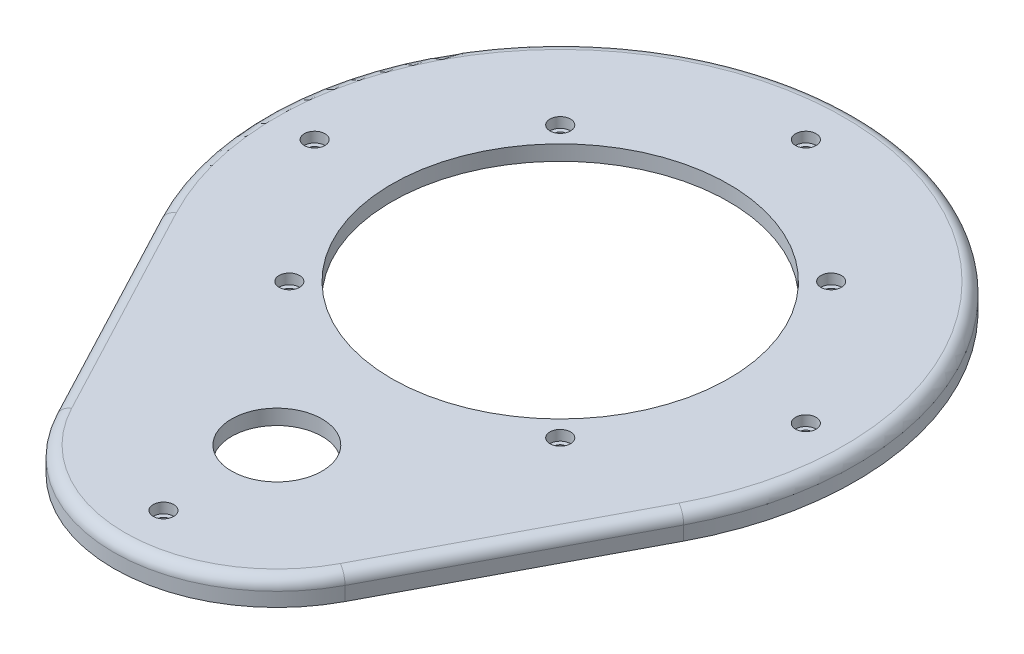
SolidWorks part; units mm, degrees
note: The reader was unsure of these and kept them because the rebuilt part matched: shared geometry of "Sketch1<3>", "Sketch1<4>", "Sketch1<5>".
ref_plane "Front Plane" through (0, 0, 0) normal (0, 0, 1) x (1, 0, 0)
ref_plane "Top Plane" through (0, 0, 0) normal (0, 1, 0) x (1, 0, 0)
ref_plane "Right Plane" through (0, 0, 0) normal (1, 0, 0) x (0, 0, -1)
sketch "Sketch1" plane through (0, 0, 0) normal (0, 1, 0) x (1, 0, 0)
  line L0 (-66.3325, -35) -> (-35.3773, -93.6667)
  line L1 (35.3773, -93.6667) -> (66.3325, -35)
  line L2 (38.2075, -95.16) -> (69.1627, -36.4933)
  line L3 (-69.1627, -36.4933) -> (-38.2075, -95.16)
  line L4 (35.5542, -93.76) -> (66.5094, -35.0933)
  line L5 (-66.5094, -35.0933) -> (-35.5542, -93.76)
  circle A0 centre (0, 0) radius 44.595
  circle A1 centre (-35.85, 35.85) radius 1.6
  circle A2 centre (35.85, 35.85) radius 1.6
  circle A3 centre (-35.85, -35.85) radius 1.6
  circle A4 centre (35.85, -35.85) radius 1.6
  circle A5 centre (0, -75) radius 11.97
  arc A6 (-66.3325, -35) -> (66.3325, -35) centre (0, 0) cw
  arc A7 (0, -115) -> (-35.3773, -93.6667) centre (0, -75) cw
  arc A8 (0, -115) -> (35.3773, -93.6667) centre (0, -75) ccw
  arc A9 (-69.1627, -36.4933) -> (69.1627, -36.4933) centre (0, 0) cw
  arc A10 (0, -118.2) -> (38.2075, -95.16) centre (0, -75) ccw
  arc A11 (0, -118.2) -> (-38.2075, -95.16) centre (0, -75) cw
  circle A12 centre (0, 65) radius 1.6
  circle A13 centre (-65, 0) radius 1.6
  circle A14 centre (65, 0) radius 1.6
  circle A15 centre (0, -105) radius 1.6
  circle A16 centre (0, 65) radius 2.725
  circle A17 centre (35.85, 35.85) radius 2.725
  circle A18 centre (65, 0) radius 2.725
  circle A19 centre (35.85, -35.85) radius 2.725
  circle A20 centre (0, -105) radius 2.725
  circle A21 centre (-35.85, -35.85) radius 2.725
  circle A22 centre (-65, 0) radius 2.725
  circle A23 centre (-35.85, 35.85) radius 2.725
  arc A24 (-66.5094, -35.0933) -> (66.5094, -35.0933) centre (0, 0) cw
  arc A25 (0, -115.2) -> (35.5542, -93.76) centre (0, -75) ccw
  arc A26 (0, -115.2) -> (-35.5542, -93.76) centre (0, -75) cw
  dimension "D1" = 89.19
  dimension "D6" = 3.2
  dimension "D7" = 3.2
  dimension "D8" = 3.2
  dimension "D9" = 3.2
  dimension "D10" = 23.94
  dimension "D12" = 40
  dimension "D13" = 75
  dimension "D15" = 3.2
  dimension "D16" = 3.2
  dimension "D17" = 3.2
  dimension "D18" = 3.2
  dimension "D23" = 5.45
  dimension "D24" = 5.45
  dimension "D25" = 5.45
  dimension "D26" = 5.45
  dimension "D27" = 5.45
  dimension "D28" = 5.45
  dimension "D29" = 5.45
  dimension "D30" = 5.45
  dimension "D2" = 71.7
  dimension "D3" = 35.85
  dimension "D4" = 35.85
  dimension "D5" = 71.7
  dimension "D11" = 75
  dimension "D19" = 65
  dimension "D20" = 65
  dimension "D21" = 65
  dimension "D22" = 30
  dimension "D14" = 3.2
  dimension "D31" = 0.2
extrude "Boss-Extrude1" add sketch "Sketch1" along normal blind 4 contours A9 L2 A10 A11 L3
extrude "Cut-Extrude3" cut sketch "Sketch1<3>" along normal through all contours A5 | A3 | A13 | A1 | A12 | A2 | A14 | A4 | A15 | A0
sketch "Sketch1<3>" plane through (0, 0, 0) normal (0, 1, 0) x (1, 0, 0) same geometry as "Sketch1"
extrude "Cut-Extrude4" cut sketch "Sketch1<4>" against normal blind 2.7 from surface at 4 contours A16 | A23 | A17 | A22 | A21 | A19 | A18 | A20 starting at face at (0, 4, 106.6)
sketch "Sketch1<4>" plane through (0, 0, 0) normal (0, 1, 0) x (1, 0, 0) same geometry as "Sketch1"
extrude "Boss-Extrude2" add sketch "Sketch1<5>" against normal blind 2.7 contours A11 A10 L2 A9 L3 A25 A26 L5 A24 L4
sketch "Sketch1<5>" plane through (0, 0, 0) normal (0, 1, 0) x (1, 0, 0) same geometry as "Sketch1"
fillet "Fillet1" radius 3 4 edges at (-53.6851, 4, 65.8267) (0, 4, 118.2) (53.6851, 4, 65.8267) (0, 4, -78.2)
